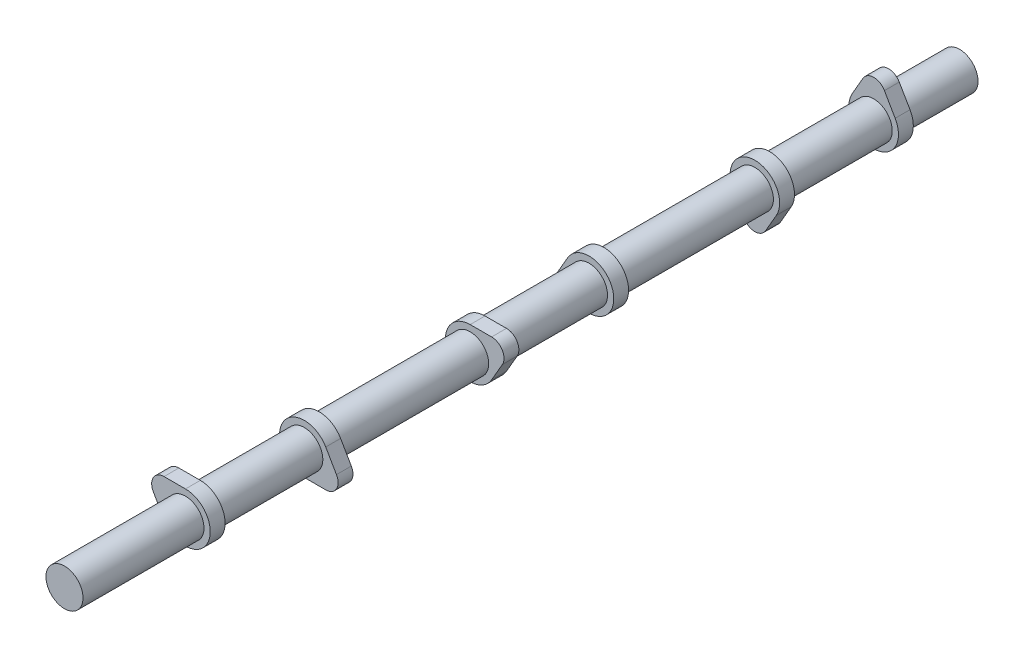
SolidWorks part; units mm, degrees
ref_plane "Front Plane" through (0, 0, 0) normal (0, 0, 1) x (1, 0, 0)
ref_plane "Top Plane" through (0, 0, 0) normal (0, 1, 0) x (1, 0, 0)
ref_plane "Right Plane" through (0, 0, 0) normal (1, 0, 0) x (0, 0, -1)
sketch "Sketch1" plane through (0, 0, 0) normal (0, 0, 1) x (1, 0, 0)
  line L2 (-5.4993, 15.875) -> (-10.9985, 6.35)
  line L3 (5.4993, 15.875) -> (10.9985, 6.35)
  arc A2 (-10.9985, 6.35) -> (10.9985, 6.35) centre (0, 0) ccw
  arc A3 (5.4993, 15.875) -> (-5.4993, 15.875) centre (0, 12.7) ccw
extrude "Boss-Extrude1" add sketch "Sketch1" along normal mid plane 7.62
ref_axis "Axis1" through (0, 0, 82.994) along (0, 0, -1)
move or copy body "Body-Move/Copy1" bodies to move or copy 113 copy yes number of copies 1 translate (0, 0, 60.96)
move or copy body "Body-Move/Copy2" bodies to move or copy 114 copy no rotation origin (0, 0, 0) rotation axis (0, 0, 1) rotation angle 180
ref_plane "Plane1" through (0, 0, -29.21) normal (0, 0, -1) x (-1, 0, 0)
sketch "Sketch2" plane through (0, 0, -29.21) normal (0, 0, -1) x (-1, 0, 0)
  line L2 (-5.4993, 15.875) -> (-10.9985, 6.35)
  line L3 (10.9985, 6.35) -> (5.4993, 15.875)
  line L4 (-5.4993, 15.875) -> (-10.9985, 6.35) construction
  line L5 (10.9985, 6.35) -> (5.4993, 15.875) construction
  circle A0 centre (0, 0) radius 9.5
  arc A2 (5.4993, 15.875) -> (-5.4993, 15.875) centre (0, 12.7) ccw
  arc A3 (-10.9985, 6.35) -> (10.9985, 6.35) centre (0, 0) ccw
  arc A4 (5.4993, 15.875) -> (-5.4993, 15.875) centre (0, 12.7) ccw construction
  arc A5 (-10.9985, 6.35) -> (10.9985, 6.35) centre (0, 0) ccw construction
  dimension "D2" = 19
  dimension "D1" = 0
extrude "Boss-Extrude2" add sketch "Sketch2" against normal blind 146.05
pattern_linear "LPattern1" count 3 spacing 146.05 along (0, 0, 1) of bodies 116
move or copy body "Body-Move/Copy3" bodies to move or copy 117 copy no rotation origin (0, 0, 0) rotation axis (0, 0, 1) rotation angle 120
move or copy body "Body-Move/Copy4" bodies to move or copy 118 copy no rotation origin (0, 0, 0) rotation axis (0, 0, -1) rotation angle 120
sketch "Sketch3" plane through (0, 0, -29.21) normal (0, 0, -1) x (-1, 0, 0)
  circle A1 centre (0, 0) radius 9.5
  circle A2 centre (0, 0) radius 9.5
  dimension "D1" = 0
extrude "Boss-Extrude3" add sketch "Sketch3" along normal blind 27.94
combine bodies "Combine1" operation type add bodies to combine 120 119 121
sketch "Sketch4" plane through (0, 0, -57.15) normal (0, 0, -1) x (-1, 0, 0)
  circle A1 centre (0, 0) radius 9.5
  circle A2 centre (0, 0) radius 9.5
  dimension "D1" = 0
extrude "Cut-Extrude1" cut sketch "Sketch4" against normal blind 16.94
sketch "Sketch5" plane through (0, 0, 408.94) normal (0, 0, 1) x (1, 0, 0)
  circle A1 centre (0, 0) radius 9.5
  circle A2 centre (0, 0) radius 9.5
  dimension "D1" = 0
extrude "Boss-Extrude4" add sketch "Sketch5" along normal blind 10
ref_plane "Plane2" through (0, 0, 353.06) normal (0, 0, 1) x (1, 0, 0)
ref_plane "Plane3" through (0, 0, 353.06) normal (0, 0, 1) x (1, 0, 0)
